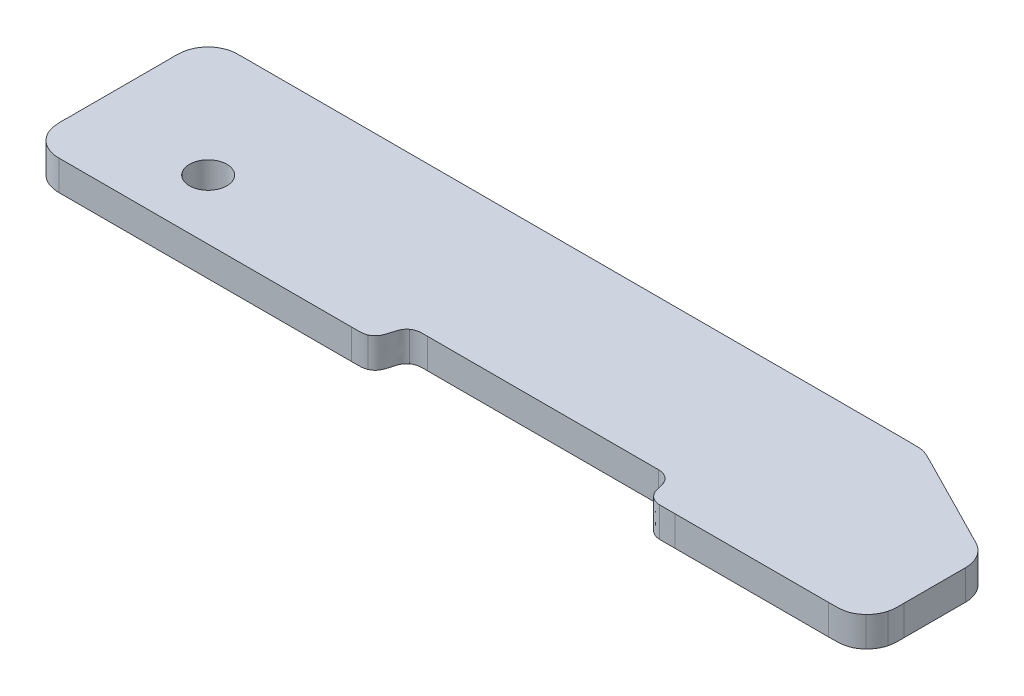
SolidWorks part; units mm, degrees
ref_plane "Front Plane" through (0, 0, 0) normal (0, 0, 1) x (1, 0, 0)
ref_plane "Top Plane" through (0, 0, 0) normal (0, 1, 0) x (1, 0, 0)
ref_plane "Right Plane" through (0, 0, 0) normal (1, 0, 0) x (0, 0, -1)
sketch "Imported Profile" plane through (0, 0, 0) normal (0, 1, 0) x (1, 0, 0)
  spline S0 degree 3 poles (178.0582, 21.1546) (178.0578, 16.8138) (178.0575, 12.466) (178.0571, 8.1183) knots 0 0 0 0 1 1 1 1
  spline S1 degree 3 poles (178.0571, 8.1183) (178.0575, 7.0503) (178.1268, 5.9962) (177.8377, 4.935) knots 0 0 0 0 1 1 1 1
  spline S2 degree 3 poles (177.8377, 4.935) (177.5208, 3.7568) (176.9764, 2.8473) (176.1014, 1.9998) knots 0 0 0 0 1 1 1 1
  spline S3 degree 3 poles (176.1014, 1.9998) (174.117, 0.105) (172.3462, 0.2359) (169.9209, 0.2359) knots 0 0 0 0 1 1 1 1
  spline S4 degree 3 poles (169.9209, 0.2359) (161.2323, 0.2359) (152.5369, 0.2359) (143.8484, 0.2359) knots 0 0 0 0 1 1 1 1
  spline S5 degree 3 poles (143.8484, 0.2359) (141.6642, 0.2359) (139.4869, 0.2359) (137.3096, 0.2359) knots 0 0 0 0 1 1 1 1
  spline S6 degree 3 poles (137.3096, 0.2359) (136.2209, 0.2359) (135.1392, 0.2014) (134.0505, 0.2359) knots 0 0 0 0 1 1 1 1
  spline S7 degree 3 poles (134.0505, 0.2359) (132.8999, 0.2704) (131.8595, 0.918) (131.3289, 1.9377) knots 0 0 0 0 1 1 1 1
  spline S8 degree 3 poles (131.3289, 1.9377) (130.819, 2.9161) (130.8811, 4.0324) (130.316, 5.0039) knots 0 0 0 0 1 1 1 1
  spline S9 degree 3 poles (130.316, 5.0039) (129.7373, 6.003) (128.6831, 6.5817) (127.5324, 6.5817) knots 0 0 0 0 1 1 1 1
  spline S10 degree 3 poles (127.5324, 6.5817) (125.3551, 6.5817) (123.1778, 6.5817) (121.0005, 6.5817) knots 0 0 0 0 1 1 1 1
  spline S11 degree 3 poles (121.0005, 6.5817) (112.2844, 6.5817) (103.5752, 6.5817) (94.8591, 6.5817) knots 0 0 0 0 1 1 1 1
  spline S12 degree 3 poles (94.8591, 6.5817) (90.5045, 6.5817) (86.143, 6.5817) (81.7815, 6.5817) knots 0 0 0 0 1 1 1 1
  spline S13 degree 3 poles (81.7815, 6.5817) (80.6929, 6.5817) (79.6042, 6.5817) (78.5156, 6.5817) knots 0 0 0 0 1 1 1 1
  spline S14 degree 3 poles (78.5156, 6.5817) (77.3994, 6.5817) (76.3727, 6.7195) (75.3461, 5.9685) knots 0 0 0 0 1 1 1 1
  spline S15 degree 3 poles (75.3461, 5.9685) (73.3755, 4.5285) (74.5055, 1.6759) (71.963, 0.5184) knots 0 0 0 0 1 1 1 1
  spline S16 degree 3 poles (71.963, 0.5184) (71.1224, 0.1325) (69.5721, 0.2359) (68.7315, 0.2359) knots 0 0 0 0 1 1 1 1
  spline S17 degree 3 poles (68.7315, 0.2359) (67.6429, 0.2359) (66.5542, 0.2359) (65.4656, 0.2359) knots 0 0 0 0 1 1 1 1
  spline S18 degree 3 poles (65.4656, 0.2359) (63.2883, 0.2359) (61.1041, 0.2359) (58.9268, 0.2359) knots 0 0 0 0 1 1 1 1
  spline S19 degree 3 poles (58.9268, 0.2359) (54.5653, 0.2359) (50.2107, 0.2359) (45.8492, 0.2359) knots 0 0 0 0 1 1 1 1
  spline S20 degree 3 poles (45.8492, 0.2359) (37.1538, 0.2359) (28.4515, 0.2359) (19.7492, 0.2359) knots 0 0 0 0 1 1 1 1
  spline S21 degree 3 poles (19.7492, 0.2359) (15.4014, 0.2359) (11.0468, 0.2359) (6.6991, 0.2359) knots 0 0 0 0 1 1 1 1
  spline S22 degree 3 poles (6.6991, 0.2359) (4.3634, 0.2359) (2.2618, 1.3865) (1.0905, 3.4329) knots 0 0 0 0 1 1 1 1
  spline S23 degree 3 poles (1.0905, 3.4329) (-0.0326, 5.4035) (0.2568, 7.8082) (0.2568, 9.8201) knots 0 0 0 0 1 1 1 1
  spline S24 degree 3 poles (0.2568, 9.8201) (0.2568, 14.1678) (0.2568, 18.5156) (0.2568, 22.8564) knots 0 0 0 0 1 1 1 1
  spline S25 degree 3 poles (0.2568, 22.8564) (0.2568, 25.0337) (0.2568, 27.2041) (0.2568, 29.3745) knots 0 0 0 0 1 1 1 1
  spline S26 degree 3 poles (0.2568, 29.3745) (0.2568, 31.6) (-0.0119, 33.6464) (1.4833, 35.6859) knots 0 0 0 0 1 1 1 1
  spline S27 degree 3 poles (1.4833, 35.6859) (2.2136, 36.685) (3.0611, 37.3464) (4.198, 37.815) knots 0 0 0 0 1 1 1 1
  spline S28 degree 3 poles (4.198, 37.815) (5.2453, 38.2422) (6.2788, 38.2835) (7.3675, 38.2835) knots 0 0 0 0 1 1 1 1
  spline S29 degree 3 poles (7.3675, 38.2835) (9.5379, 38.2835) (11.7083, 38.2835) (13.8856, 38.2835) knots 0 0 0 0 1 1 1 1
  spline S30 degree 3 poles (13.8856, 38.2835) (18.2264, 38.2835) (22.5741, 38.2835) (26.9218, 38.2835) knots 0 0 0 0 1 1 1 1
  spline S31 degree 3 poles (26.9218, 38.2835) (44.4092, 38.2835) (61.8964, 38.2835) (79.3906, 38.2835) knots 0 0 0 0 1 1 1 1
  spline S32 degree 3 poles (79.3906, 38.2835) (96.8573, 38.2835) (114.3308, 38.2835) (131.7975, 38.2835) knots 0 0 0 0 1 1 1 1
  spline S33 degree 3 poles (131.7975, 38.2835) (136.1589, 38.2835) (140.5273, 38.2835) (144.8888, 38.2835) knots 0 0 0 0 1 1 1 1
  spline S34 degree 3 poles (144.8888, 38.2835) (145.4745, 38.2835) (150.8419, 38.304) (151.4345, 38.2216) knots 0 0 0 0 1 1 1 1
  spline S35 degree 3 poles (151.4345, 38.2216) (152.5645, 38.063) (153.5015, 37.5601) (154.48, 37.0571) knots 0 0 0 0 1 1 1 1
  spline S36 degree 3 poles (154.48, 37.0571) (155.4515, 36.5679) (156.423, 36.0718) (157.3945, 35.5757) knots 0 0 0 0 1 1 1 1
  spline S37 degree 3 poles (157.3945, 35.5757) (161.2875, 33.5914) (165.1735, 31.6139) (169.0665, 29.6295) knots 0 0 0 0 1 1 1 1
  spline S38 degree 3 poles (169.0665, 29.6295) (170.038, 29.1334) (171.0095, 28.6373) (171.981, 28.1412) knots 0 0 0 0 1 1 1 1
  spline S39 degree 3 poles (171.981, 28.1412) (172.9526, 27.652) (173.9379, 27.1973) (174.8818, 26.6529) knots 0 0 0 0 1 1 1 1
  spline S40 degree 3 poles (174.8818, 26.6529) (176.8455, 25.523) (178.0582, 23.4214) (178.0582, 21.1546) knots 0 0 0 0 1 1 1 1
  spline S41 degree 3 poles (29.6228, 12.9345) (29.6228, 10.7434) (27.8451, 8.9657) (25.6541, 8.9657) knots 0 0 0 0 1 1 1 1
  spline S42 degree 3 poles (25.6541, 8.9657) (23.463, 8.9657) (21.6853, 10.7434) (21.6853, 12.9345) knots 0 0 0 0 1 1 1 1
  spline S43 degree 3 poles (21.6853, 12.9345) (21.6853, 15.1256) (23.463, 16.9032) (25.6541, 16.9032) knots 0 0 0 0 1 1 1 1
  spline S44 degree 3 poles (25.6541, 16.9032) (27.8451, 16.9032) (29.6228, 15.1256) (29.6228, 12.9345) knots 0 0 0 0 1 1 1 1
  point P0 (178.0582, 21.1379)
sketch "Sketch4" plane through (0, 0, 0) normal (0, 1, 0) x (1, 0, 0)
  circle A0 centre (25.6541, 12.9345) radius 3.9688
  spline S0 degree 3 poles (-1370.1409, 1323.9207) (1038.8939, -923.7451) (-712.4339, 988.9517) (1696.6083, -1258.7214) knots -41.774564 -41.774564 -41.774564 -41.774564 42.774639 42.774639 42.774639 42.774639 only from (157.3945, 35.5757) to (169.0665, 29.6295) construction
  spline S1 degree 3 poles (376.0605, 1875.4206) (-1479.5997, -1082.3544) (1829.0874, 1138.1816) (-51.3256, -1816.4188) knots -369.840284 -369.840284 -369.840284 -369.840284 371.612933 371.612933 371.612933 371.612933 only from (169.0665, 29.6295) to (171.981, 28.1412) construction
  spline S2 degree 3 poles (908.269, 1887.0169) (-659.8258, -1783.9957) (1006.9937, 1838.9417) (-567.5164, -1829.9023) knots -24.219115 -24.219115 -24.219115 -24.219115 24.76741 24.76741 24.76741 24.76741 only from (171.981, 28.1412) to (174.8818, 26.6529) construction
  spline S3 degree 3 poles (634.5941, -1913.7013) (-663.7986, 1873.0389) (1345.8725, -1636.8189) (-1263.0141, 1399.4192) knots -12.393463 -12.393463 -12.393463 -12.393463 13.40497 13.40497 13.40497 13.40497 only from (174.8818, 26.6529) to (178.0582, 21.1546) construction
  spline S4 degree 3 poles (177.8889, -1978.7637) (178.3368, 3312.0916) (177.7768, -3302.3891) (178.2264, 2008.1061) knots -74.483894 -74.483894 -74.483894 -74.483894 76.608418 76.608418 76.608418 76.608418 only from (178.0582, 21.1546) to (178.0571, 8.1183) construction
  spline S5 degree 3 poles (2171.4545, 166.8586) (-1816.6914, -74.7286) (2173.4037, 84.1055) (-1817.1039, -134.2335) knots -16.54842 -16.54842 -16.54842 -16.54842 16.876064 16.876064 16.876064 16.876064 only from (178.0571, 8.1183) to (177.8377, 4.935) construction
  spline S6 degree 3 poles (709.4157, 1930.8999) (-539.7061, -1730.6163) (1128.2343, 1617.8505) (-1058.8853, -1567.9445) knots -19.565605 -19.565605 -19.565605 -19.565605 20.7495 20.7495 20.7495 20.7495 only from (177.8377, 4.935) to (176.1014, 1.9998) construction
  spline S7 degree 3 poles (833.5382, 1890.7975) (-498.1038, -1848.355) (931.456, 1807.4864) (-764.8748, -1766.3119) knots -8.63166 -8.63166 -8.63166 -8.63166 10.296247 10.296247 10.296247 10.296247 only from (176.1014, 1.9998) to (169.9209, 0.2359) construction
  spline S8 degree 3 poles (-1830.031, 0.2359) (4381.8556, 0.2359) (-4068.1572, 0.2359) (2143.7916, 0.2359) knots -63.871392 -63.871392 -63.871392 -63.871392 64.873514 64.873514 64.873514 64.873514 only from (169.9209, 0.2359) to (143.8484, 0.2359) construction
  spline S9 degree 3 poles (2143.7844, 0.2359) (-1331.6123, 0.2359) (1604.7294, 0.2359) (-1862.6509, 0.2359) knots -60.473146 -60.473146 -60.473146 -60.473146 62.39629 62.39629 62.39629 62.39629 only from (143.8484, 0.2359) to (137.3096, 0.2359) construction
  spline S10 degree 3 poles (490.5198, -1967.6601) (-98.9506, 1969.9859) (368.1575, -1970.1717) (-208.4723, 1970.0419) knots -26.362878 -26.362878 -26.362878 -26.362878 27.038245 27.038245 27.038245 27.038245 only from (137.3096, 0.2359) to (134.0505, 0.2359) construction
  spline S11 degree 3 poles (-1291.7134, 1397.3141) (1777.1165, -1170.1098) (-1670.4385, 908.9937) (2031.8713, -608.5517) knots -15.752288 -15.752288 -15.752288 -15.752288 16.705304 16.705304 16.705304 16.705304 only from (134.0505, 0.2359) to (131.3289, 1.9377) construction
  spline S12 degree 3 poles (2085.5986, 426.3777) (-1812.936, -467.9319) (2074.8556, 473.9409) (-1824.4844, -417.1797) knots -11.275893 -11.275893 -11.275893 -11.275893 12.231094 12.231094 12.231094 12.231094 only from (131.3289, 1.9377) to (130.316, 5.0039) construction
  spline S13 degree 3 poles (-1843.081, 303.1764) (2044.6357, -616.4683) (-1660.8929, 930.7797) (1720.8277, -1194.9113) knots -16.246574 -16.246574 -16.246574 -16.246574 17.589455 17.589455 17.589455 17.589455 only from (130.316, 5.0039) to (127.5324, 6.5817) construction
  spline S14 degree 3 poles (-1872.393, 6.5817) (6146.2332, 6.5817) (-5897.6947, 6.5817) (2120.9175, 6.5817) knots -461.690422 -461.690422 -461.690422 -461.690422 462.690096 462.690096 462.690096 462.690096 only from (127.5324, 6.5817) to (121.0005, 6.5817) construction
  spline S15 degree 3 poles (2120.9851, 6.5817) (-481.4997, 6.5817) (697.3592, 6.5817) (-1905.1308, 6.5817) knots -40.349467 -40.349467 -40.349467 -40.349467 41.349524 41.349524 41.349524 41.349524 only from (121.0005, 6.5817) to (94.8591, 6.5817) construction
  spline S16 degree 3 poles (-1905.0989, 6.5817) (3392.2369, 6.5817) (-3235.2001, 6.5817) (2081.7359, 6.5817) knots -74.617885 -74.617885 -74.617885 -74.617885 76.742175 76.742175 76.742175 76.742175 only from (94.8591, 6.5817) to (81.7815, 6.5817) construction
  spline S17 degree 3 poles (-1918.1787, 6.5817) (3831.2809, 6.5817) (-3670.9821, 6.5817) (2078.4727, 6.5817) knots -402.015798 -402.015798 -402.015798 -402.015798 403.015652 403.015652 403.015652 403.015652 only from (81.7815, 6.5817) to (78.5156, 6.5817) construction
  spline S18 degree 3 poles (328.2274, 1990.6477) (-93.8184, -1981.2991) (226.0489, 1997.3818) (-100.5912, -1986.1981) knots -12.323971 -12.323971 -12.323971 -12.323971 12.610585 12.610585 12.610585 12.610585 only from (78.5156, 6.5817) to (75.3461, 5.9685) construction
  spline S19 degree 3 poles (1909.0335, -792.0449) (-1746.7322, 853.3885) (1894.4289, -847.3372) (-1760.6043, 801.1145) knots -6.000439 -6.000439 -6.000439 -6.000439 6.915353 6.915353 6.915353 6.915353 only from (75.3461, 5.9685) to (71.963, 0.5184) construction
  spline S20 degree 3 poles (-1741.4222, 843.5146) (1951.0212, -802.4628) (-1827.6146, 763.5106) (1932.5612, -724.841) knots -10.425283 -10.425283 -10.425283 -10.425283 11.524314 11.524314 11.524314 11.524314 only from (71.963, 0.5184) to (68.7315, 0.2359) construction
  spline S21 degree 3 poles (2068.7081, 0.2359) (-494.9121, 0.2359) (625.9794, 0.2359) (-1934.5108, 0.2359) knots -330.094334 -330.094334 -330.094334 -330.094334 331.813063 331.813063 331.813063 331.813063 only from (68.7315, 0.2359) to (65.4656, 0.2359) construction
  spline S22 degree 3 poles (-1934.4558, 0.2359) (2544.0676, 0.2359) (-2419.691, 0.2359) (2058.8868, 0.2359) knots -55.124015 -55.124015 -55.124015 -55.124015 56.124335 56.124335 56.124335 56.124335 only from (65.4656, 0.2359) to (58.9268, 0.2359) construction
  spline S23 degree 3 poles (2058.9124, 0.2359) (-1141.0787, 0.2359) (1245.8467, 0.2359) (-1954.0877, 0.2359) knots -46.140285 -46.140285 -46.140285 -46.140285 47.139812 47.139812 47.139812 47.139812 only from (58.9268, 0.2359) to (45.8492, 0.2359) construction
  spline S24 degree 3 poles (-1954.0586, 0.2359) (4959.9478, 0.2359) (-4936.8779, 0.2359) (2019.6311, 0.2359) knots -83.969481 -83.969481 -83.969481 -83.969481 86.191752 86.191752 86.191752 86.191752 only from (45.8492, 0.2359) to (19.7492, 0.2359) construction
  spline S25 degree 3 poles (-1980.2129, 0.2359) (3024.9489, 0.2359) (-2998.4869, 0.2359) (2006.6319, 0.2359) knots -58.007247 -58.007247 -58.007247 -58.007247 59.007019 59.007019 59.007019 59.007019 only from (19.7492, 0.2359) to (6.6991, 0.2359) construction
  spline S26 degree 3 poles (-1518.6587, 1280.0571) (1804.2894, -892.1883) (-1949.0224, 475.8394) (1993.1986, -27.5117) knots -13.599929 -13.599929 -13.599929 -13.599929 14.087522 14.087522 14.087522 14.087522 only from (6.6991, 0.2359) to (1.0905, 3.4329) construction
  spline S27 degree 3 poles (1850.5432, 762.9152) (-1832.6938, -877.3868) (1813.9623, 937.6913) (-1792.4897, -876.4778) knots -9.455497 -9.455497 -9.455497 -9.455497 11.007676 11.007676 11.007676 11.007676 only from (1.0905, 3.4329) to (0.2568, 9.8201) construction
  spline S28 degree 3 poles (0.2568, 2009.7703) (0.2568, -3300.6804) (0.2568, 3313.8414) (0.2568, -1977.1345) knots -75.608062 -75.608062 -75.608062 -75.608062 75.484586 75.484586 75.484586 75.484586 only from (0.2568, 9.8201) to (0.2568, 22.8564) construction
  spline S29 degree 3 poles (0.2568, -1977.0858) (0.2568, 1498.0415) (0.2568, -1437.7248) (0.2568, 2029.2923) knots -60.694704 -60.694704 -60.694704 -60.694704 62.624087 62.624087 62.624087 62.624087 only from (0.2568, 22.8564) to (0.2568, 29.3745) construction
  spline S30 degree 3 poles (-1979.6988, -248.5886) (1985.873, 192.3153) (-1989.6613, -101.2351) (1993.0338, 217.8919) knots -9.782615 -9.782615 -9.782615 -9.782615 10.068378 10.068378 10.068378 10.068378 only from (0.2568, 29.3745) to (1.4833, 35.6859) construction
  spline S31 degree 3 poles (-1232.7755, -1535.103) (1340.6323, 1343.5524) (-1511.5406, -1057.7752) (1768.3466, 974.3779) knots -19.756295 -19.756295 -19.756295 -19.756295 20.879982 20.879982 20.879982 20.879982 only from (1.4833, 35.6859) to (4.198, 37.815) construction
  spline S32 degree 3 poles (-383.1861, -1924.2448) (358.5547, 1991.6677) (-381.6585, -1905.6519) (513.4478, 1972.461) knots -16.73895 -16.73895 -16.73895 -16.73895 18.892251 18.892251 18.892251 18.892251 only from (4.198, 37.815) to (7.3675, 38.2835) construction
  spline S33 degree 3 poles (-1992.578, 38.2835) (1476.3701, 38.2835) (-1463.0889, 38.2835) (2013.8636, 38.2835) knots -61.407639 -61.407639 -61.407639 -61.407639 61.491697 61.491697 61.491697 61.491697 only from (7.3675, 38.2835) to (13.8856, 38.2835) construction
  spline S34 degree 3 poles (2013.8663, 38.2835) (-3282.4938, 38.2835) (3342.9854, 38.2835) (-1973.0515, 38.2835) knots -74.794721 -74.794721 -74.794721 -74.794721 76.92726 76.92726 76.92726 76.92726 only from (13.8856, 38.2835) to (26.9218, 38.2835) construction
  spline S35 degree 3 poles (-1973.0671, 38.2835) (-282.1228, 38.2835) (366.949, 38.2835) (2079.3673, 38.2835) knots -33.258534 -33.258534 -33.258534 -33.258534 33.951426 33.951426 33.951426 33.951426 only from (26.9218, 38.2835) to (79.3906, 38.2835) construction
  spline S36 degree 3 poles (79.3798, 38.2835) (-4648.3375, 38.2835) (6497.4658, 38.2835) (-1868.1201, 38.2835) knots -60.949289 -60.949289 -60.949289 -60.949289 76.032141 76.032141 76.032141 76.032141 only from (79.3906, 38.2835) to (131.7975, 38.2835) construction
  spline S37 degree 3 poles (2131.7334, 38.2835) (-2877.58, 38.2835) (3154.3213, 38.2835) (-1855.0887, 38.2835) knots -58.064419 -58.064419 -58.064419 -58.064419 59.06678 59.06678 59.06678 59.06678 only from (131.7975, 38.2835) to (144.8888, 38.2835) construction
  spline S38 degree 3 poles (2144.6774, 60.5049) (-1919.6384, 13.355) (2215.9334, 66.1673) (-1848.2672, 7.1957) knots -5.485793 -5.485793 -5.485793 -5.485793 6.486432 6.486432 6.486432 6.486432 only from (144.8888, 38.2835) to (151.4345, 38.2216) construction
  spline S39 degree 3 poles (-992.6085, -1602.0212) (1251.1464, 1698.4933) (-958.1323, -1612.5578) (1348.0175, 1641.3866) knots -15.910235 -15.910235 -15.910235 -15.910235 17.791712 17.791712 17.791712 17.791712 only from (151.4345, 38.2216) to (154.48, 37.0571) construction
  spline S40 degree 3 poles (-53.3601, -1948.7709) (107.4351, 2153.4705) (207.1509, -2082.6357) (368.8715, 2020.8147) knots -66.150823 -66.150823 -66.150823 -66.150823 68.16056 68.16056 68.16056 68.16056 only from (154.48, 37.0571) to (157.3945, 35.5757) construction
  spline S41 degree 3 poles (157.3945, 35.5757) (161.2875, 33.5914) (165.1735, 31.6139) (169.0665, 29.6295) knots 0 0 0 0 1 1 1 1
  spline S42 degree 3 poles (169.0665, 29.6295) (170.038, 29.1334) (171.0095, 28.6373) (171.981, 28.1412) knots 0 0 0 0 1 1 1 1
  spline S43 degree 3 poles (171.981, 28.1412) (172.9526, 27.652) (173.9379, 27.1973) (174.8818, 26.6529) knots 0 0 0 0 1 1 1 1
  spline S44 degree 3 poles (174.8818, 26.6529) (176.8457, 25.5229) (178.0584, 23.4211) (178.0582, 21.154) knots 0 0 0 0 1.000079 1.000079 1.000079 1.000079
  spline S45 degree 3 poles (178.0582, 21.154) (178.0578, 16.8134) (178.0575, 12.4659) (178.0571, 8.1183) knots 0.000041 0.000041 0.000041 0.000041 1 1 1 1
  spline S46 degree 3 poles (178.0571, 8.1183) (178.0575, 7.0503) (178.1268, 5.9962) (177.8377, 4.935) knots 0 0 0 0 1 1 1 1
  spline S47 degree 3 poles (177.8377, 4.935) (177.5208, 3.7568) (176.9764, 2.8473) (176.1014, 1.9998) knots 0 0 0 0 1 1 1 1
  spline S48 degree 3 poles (176.1014, 1.9998) (174.117, 0.105) (172.3462, 0.2359) (169.9209, 0.2359) knots 0 0 0 0 1 1 1 1
  spline S49 degree 3 poles (169.9209, 0.2359) (161.2323, 0.2359) (152.5369, 0.2359) (143.8484, 0.2359) knots 0 0 0 0 1 1 1 1
  spline S50 degree 3 poles (143.8484, 0.2359) (141.6642, 0.2359) (139.4869, 0.2359) (137.3096, 0.2359) knots 0 0 0 0 1 1 1 1
  spline S51 degree 3 poles (137.3096, 0.2359) (136.2209, 0.2359) (135.1392, 0.2014) (134.0505, 0.2359) knots 0 0 0 0 1 1 1 1
  spline S52 degree 3 poles (134.0505, 0.2359) (132.8999, 0.2704) (131.8595, 0.918) (131.3289, 1.9377) knots 0 0 0 0 1 1 1 1
  spline S53 degree 3 poles (131.3289, 1.9377) (130.819, 2.9161) (130.8811, 4.0324) (130.316, 5.0039) knots 0 0 0 0 1 1 1 1
  spline S54 degree 3 poles (130.316, 5.0039) (129.7373, 6.003) (128.6831, 6.5817) (127.5324, 6.5817) knots 0 0 0 0 1 1 1 1
  spline S55 degree 3 poles (127.5324, 6.5817) (125.3551, 6.5817) (123.1778, 6.5817) (121.0005, 6.5817) knots 0 0 0 0 1 1 1 1
  spline S56 degree 3 poles (121.0005, 6.5817) (112.2844, 6.5817) (103.5752, 6.5817) (94.8591, 6.5817) knots 0 0 0 0 1 1 1 1
  spline S57 degree 3 poles (94.8591, 6.5817) (90.5045, 6.5817) (86.143, 6.5817) (81.7815, 6.5817) knots 0 0 0 0 1 1 1 1
  spline S58 degree 3 poles (81.7815, 6.5817) (80.6929, 6.5817) (79.6042, 6.5817) (78.5156, 6.5817) knots 0 0 0 0 1 1 1 1
  spline S59 degree 3 poles (78.5156, 6.5817) (77.3994, 6.5817) (76.3727, 6.7195) (75.3461, 5.9685) knots 0 0 0 0 1 1 1 1
  spline S60 degree 3 poles (75.3461, 5.9685) (73.3755, 4.5285) (74.5055, 1.6759) (71.963, 0.5184) knots 0 0 0 0 1 1 1 1
  spline S61 degree 3 poles (71.963, 0.5184) (71.1224, 0.1325) (69.5721, 0.2359) (68.7315, 0.2359) knots 0 0 0 0 1 1 1 1
  spline S62 degree 3 poles (68.7315, 0.2359) (67.6429, 0.2359) (66.5542, 0.2359) (65.4656, 0.2359) knots 0 0 0 0 1 1 1 1
  spline S63 degree 3 poles (65.4656, 0.2359) (63.2883, 0.2359) (61.1041, 0.2359) (58.9268, 0.2359) knots 0 0 0 0 1 1 1 1
  spline S64 degree 3 poles (58.9268, 0.2359) (54.5653, 0.2359) (50.2107, 0.2359) (45.8492, 0.2359) knots 0 0 0 0 1 1 1 1
  spline S65 degree 3 poles (45.8492, 0.2359) (37.1538, 0.2359) (28.4515, 0.2359) (19.7492, 0.2359) knots 0 0 0 0 1 1 1 1
  spline S66 degree 3 poles (19.7492, 0.2359) (15.4014, 0.2359) (11.0468, 0.2359) (6.6991, 0.2359) knots 0 0 0 0 1 1 1 1
  spline S67 degree 3 poles (6.6991, 0.2359) (4.3634, 0.2359) (2.2618, 1.3865) (1.0905, 3.4329) knots 0 0 0 0 1 1 1 1
  spline S68 degree 3 poles (1.0905, 3.4329) (-0.0326, 5.4035) (0.2568, 7.8082) (0.2568, 9.8201) knots 0 0 0 0 1 1 1 1
  spline S69 degree 3 poles (0.2568, 9.8201) (0.2568, 14.1678) (0.2568, 18.5156) (0.2568, 22.8564) knots 0 0 0 0 1 1 1 1
  spline S70 degree 3 poles (0.2568, 22.8564) (0.2568, 25.0337) (0.2568, 27.2041) (0.2568, 29.3745) knots 0 0 0 0 1 1 1 1
  spline S71 degree 3 poles (0.2568, 29.3745) (0.2568, 31.6) (-0.0119, 33.6464) (1.4833, 35.6859) knots 0 0 0 0 1 1 1 1
  spline S72 degree 3 poles (1.4833, 35.6859) (2.2136, 36.685) (3.0611, 37.3464) (4.198, 37.815) knots 0 0 0 0 1 1 1 1
  spline S73 degree 3 poles (4.198, 37.815) (5.2453, 38.2422) (6.2788, 38.2835) (7.3675, 38.2835) knots 0 0 0 0 1 1 1 1
  spline S74 degree 3 poles (7.3675, 38.2835) (9.5379, 38.2835) (11.7083, 38.2835) (13.8856, 38.2835) knots 0 0 0 0 1 1 1 1
  spline S75 degree 3 poles (13.8856, 38.2835) (18.2264, 38.2835) (22.5741, 38.2835) (26.9218, 38.2835) knots 0 0 0 0 1 1 1 1
  spline S76 degree 3 poles (26.9218, 38.2835) (44.4092, 38.2835) (61.8964, 38.2835) (79.3906, 38.2835) knots 0 0 0 0 1 1 1 1
  spline S77 degree 3 poles (79.3906, 38.2835) (96.8573, 38.2835) (114.3308, 38.2835) (131.7975, 38.2835) knots 0 0 0 0 1 1 1 1
  spline S78 degree 3 poles (131.7975, 38.2835) (136.1589, 38.2835) (140.5273, 38.2835) (144.8888, 38.2835) knots 0 0 0 0 1 1 1 1
  spline S79 degree 3 poles (144.8888, 38.2835) (145.4745, 38.2835) (150.8419, 38.304) (151.4345, 38.2216) knots 0 0 0 0 1 1 1 1
  spline S80 degree 3 poles (151.4345, 38.2216) (152.5645, 38.063) (153.5015, 37.5601) (154.48, 37.0571) knots 0 0 0 0 1 1 1 1
  spline S81 degree 3 poles (154.48, 37.0571) (155.4515, 36.5679) (156.423, 36.0718) (157.3945, 35.5757) knots 0 0 0 0 1 1 1 1
extrude "Boss-Extrude1" add sketch "Sketch4" along normal blind 6.35
